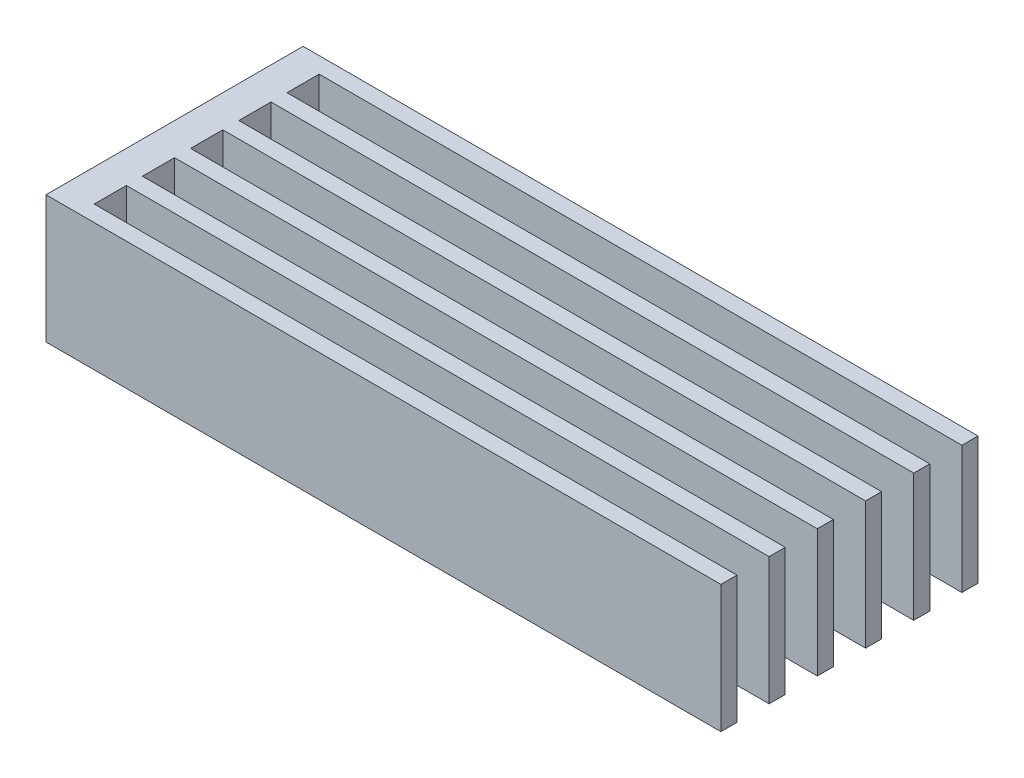
SolidWorks part; units mm, degrees
note: The reader was unsure of these and kept them because the rebuilt part matched: shared geometry of "Sketch1<4>".
other "Markup1"
sketch "Sketch2" plane through (-10.581, 7.9375, -20.4138) normal (-0.6776, 0.699, -0.2286) x (0.5538, 0.6896, 0.4667)
material "6061 Alloy"
ref_plane "Front Plane" through (0, 0, 0) normal (0, 0, 1) x (1, 0, 0)
ref_plane "Top Plane" through (0, 0, 0) normal (0, 1, 0) x (1, 0, 0)
ref_plane "Right Plane" through (0, 0, 0) normal (1, 0, 0) x (0, 0, -1)
sketch "Sketch1" plane through (0, 0, 0) normal (0, 1, 0) x (1, 0, 0)
  line L3 (-8.581, 20.4138) -> (-8.581, 4.4138)
  line L4 (-10.581, 20.4138) -> (-10.581, 4.4138)
  line L5 (-10.581, 4.4138) -> (-8.581, 4.4138)
  line L7 (-10.581, 20.4138) -> (-8.581, 20.4138)
  line L9 (-8.581, 20.4138) -> (31.419, 20.4138)
  line L10 (-8.581, 20.4138) -> (-8.581, 19.4138)
  line L11 (-8.581, 19.4138) -> (31.419, 19.4138)
  line L12 (31.419, 20.4138) -> (31.419, 19.4138)
  dimension "D1" = 2
  dimension "D2" = 16
  dimension "D8" = 40
  dimension "D9" = 1
extrude "Boss-Extrude1" add sketch "Sketch1" along normal blind 7.9375
extrude "Boss-Extrude2" add sketch "Sketch1<4>" along normal blind 7.9375
sketch "Sketch1<4>" plane through (0, 0, 0) normal (0, 1, 0) x (1, 0, 0) same geometry as "Sketch1"
pattern_linear "LPattern1" count 6 spacing 3 along (0, 0, 1) of "Boss-Extrude2"
